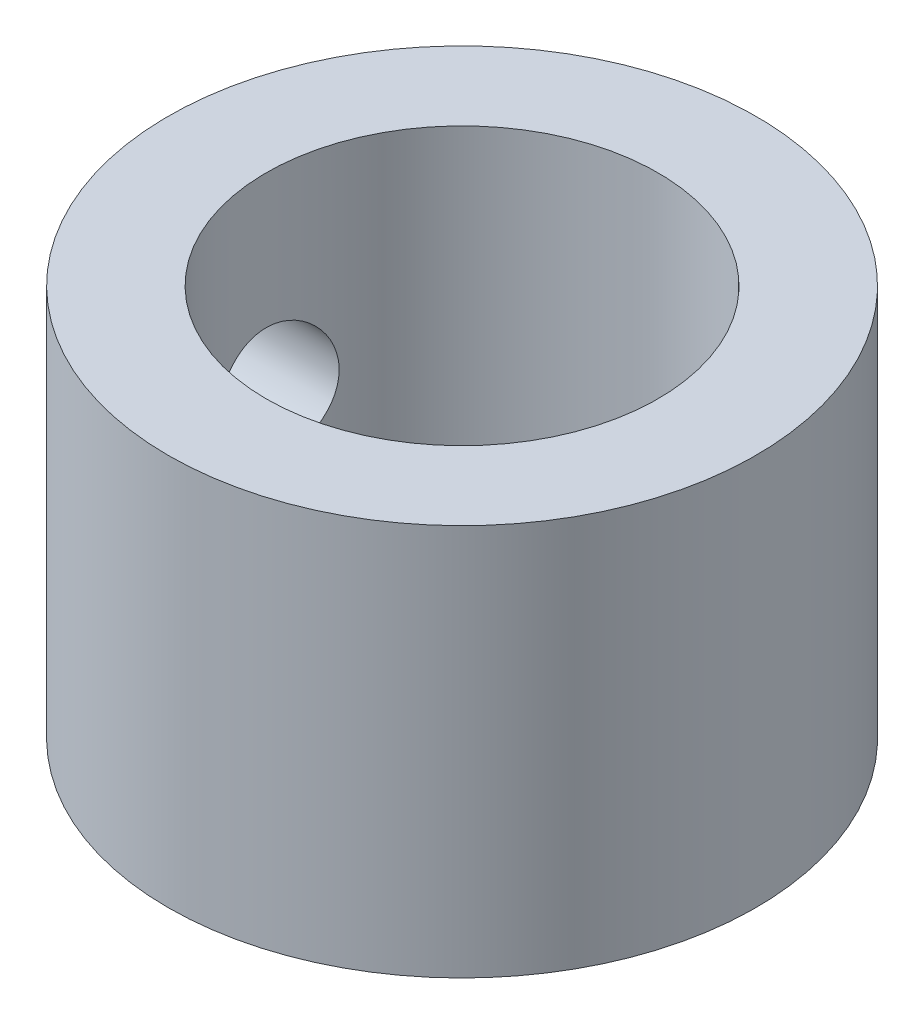
SolidWorks part; units mm, degrees
ref_plane "Front Plane" through (0, 0, 0) normal (0, 0, 1) x (1, 0, 0)
ref_plane "Top Plane" through (0, 0, 0) normal (0, 1, 0) x (1, 0, 0)
ref_plane "Right Plane" through (0, 0, 0) normal (1, 0, 0) x (0, 0, -1)
sketch "Sketch1" plane through (0, 0, 0) normal (0, 1, 0) x (1, 0, 0)
  circle A0 centre (0, 0) radius 9.525
  dimension "D1" = 19.05
extrude "Boss-Extrude1" add sketch "Sketch1" along normal blind 12.7
sketch "Sketch2" plane through (0, 12.7, 0) normal (0, 1, 0) x (1, 0, 0)
  circle A0 centre (0, 0) radius 6.35
  dimension "D1" = 12.7
extrude "Cut-Extrude1" cut sketch "Sketch2" against normal blind 9.525
sketch "Sketch3" plane through (0, 0, 0) normal (1, 0, 0) x (0, 0, -1)
  circle A0 centre (0, 6.3188) radius 2.032
  dimension "D1" = 4.064
extrude "Cut-Extrude2" cut sketch "Sketch3" against normal through all
